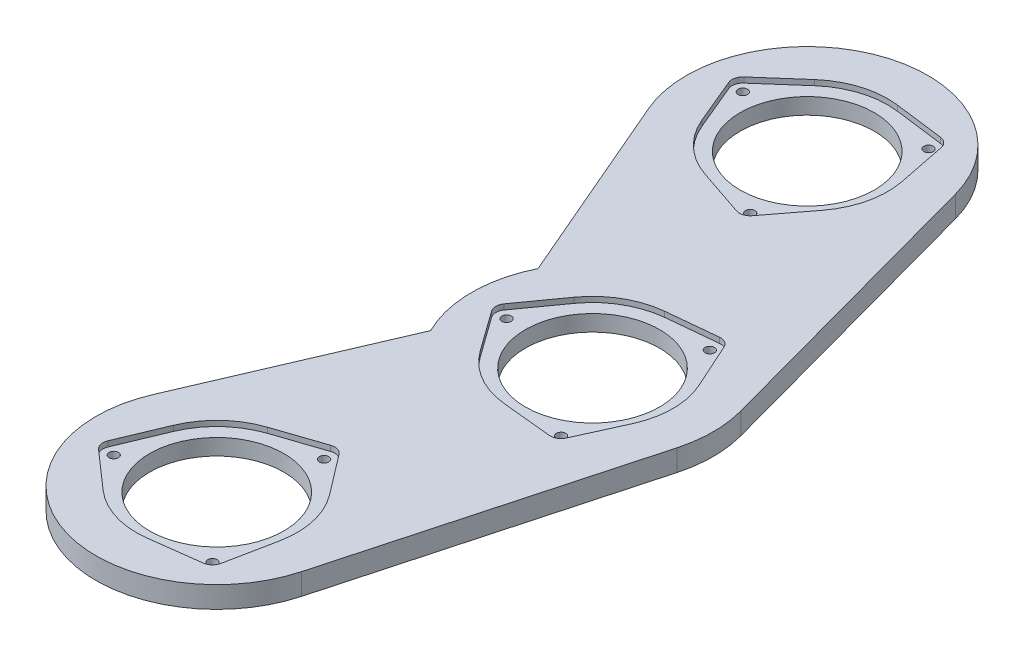
SolidWorks part; units mm, degrees
ref_plane "Alzado" through (0, 0, 0) normal (0, 0, 1) x (1, 0, 0)
ref_plane "Planta" through (0, 0, 0) normal (0, 1, 0) x (1, 0, 0)
ref_plane "Vista lateral" through (0, 0, 0) normal (1, 0, 0) x (0, 0, -1)
sketch "Croquis5" plane through (0, 0, 0) normal (0, 1, 0) x (1, 0, 0)
  line L0 (0, 176.3184) -> (0, -176.3184) construction
  line L1 (-217.2635, 0) -> (217.2635, 0) construction
  line L2 (13.4144, 121.8403) -> (43.4144, 11.8403)
  line L3 (43.4144, -11.8403) -> (13.4144, -121.8403)
  line L6 (-71.3458, 92.237) -> (-40.3113, 20)
  line L7 (-71.3458, -92.237) -> (-40.3113, -20)
  circle A0 centre (0, 0) radius 45
  circle A1 centre (-30, 110) radius 45
  circle A2 centre (-30, -110) radius 45
  point P6 (0, 0)
  point P9 (0, 0)
  point P21 (0, 0)
  point P22 (-34.641, 20)
  dimension "D1" = 90
  dimension "D2" = 220
  dimension "D3" = 30
  dimension "D4" = 20
sketch "Croquis1" plane through (0, 0, 0) normal (0, 1, 0) x (1, 0, 0)
  line L16 (-71.3458, 92.237) -> (-40.3113, 20) construction
  line L17 (-71.3458, -92.237) -> (-40.3113, -20) construction
  line L18 (43.4144, -11.8403) -> (13.4144, -121.8403) construction
  line L19 (13.4144, 121.8403) -> (43.4144, 11.8403) construction
  line L20 (-71.3458, 92.237) -> (-40.3113, 20)
  line L21 (-71.3458, -92.237) -> (-40.3113, -20)
  line L22 (43.4144, -11.8403) -> (13.4144, -121.8403)
  line L23 (13.4144, 121.8403) -> (43.4144, 11.8403)
  circle A10 centre (-30, -110) radius 45 construction
  circle A11 centre (0, 0) radius 45 construction
  circle A12 centre (-30, 110) radius 45 construction
  arc A13 (-71.3458, -92.237) -> (13.4144, -121.8403) centre (-30, -110) ccw
  arc A14 (-40.3113, 20) -> (-40.3113, -20) centre (0, 0) ccw
  arc A15 (13.4144, 121.8403) -> (-71.3458, 92.237) centre (-30, 110) ccw
  arc A16 (43.4144, -11.8403) -> (43.4144, 11.8403) centre (0, 0) ccw
extrude "Saliente-Extruir1" add sketch "Croquis1" along normal blind 8
sketch "Croquis6" plane through (0, 8, 0) normal (0, 1, 0) x (1, 0, 0)
  line L0 (-17.4639, -76.972) -> (-6.1488, -91.8033)
  line L1 (-39.5981, -81.5768) -> (-21.9239, -75.6085)
  line L2 (0, 0) -> (-32, 0) construction
  line L3 (-24.375, -17.4888) -> (-35.25, -2.3318)
  line L4 (-35.25, 2.3318) -> (-24.375, 17.4888)
  line L5 (-2.9583, 29.8538) -> (15.6056, 31.6933)
  line L6 (19.6444, 29.3615) -> (27.3333, 12.365)
  line L7 (27.3333, -12.365) -> (19.6444, -29.3615)
  line L8 (15.6056, -31.6933) -> (-2.9583, -29.8538)
  line L9 (-7.665, -137.3705) -> (-26.1668, -139.7541)
  line L10 (-49.8161, -132.5238) -> (-63.822, -120.2016)
  line L11 (-0.5858, -115.8994) -> (-4.2542, -134.1899)
  line L12 (-30, -110) -> (-61.1798, -117.1984) construction
  line L13 (-64.8711, -115.6574) -> (-57.6844, -98.4426)
  line L14 (-64.8711, 115.6574) -> (-57.6844, 98.4426)
  line L15 (-0.5858, 115.8994) -> (-4.2542, 134.1899)
  line L16 (-49.8161, 132.5238) -> (-63.822, 120.2016)
  line L17 (-7.665, 137.3705) -> (-26.1668, 139.7541)
  line L18 (-39.5981, 81.5768) -> (-21.9239, 75.6085)
  line L19 (-17.4639, 76.972) -> (-6.1488, 91.8033)
  arc A0 (-24.375, -17.4888) -> (-2.9583, -29.8538) centre (0, 0) ccw
  arc A3 (-35.25, 2.3318) -> (-35.25, -2.3318) centre (-32, 0) ccw
  arc A4 (19.6444, 29.3615) -> (15.6056, 31.6933) centre (16, 27.7128) ccw
  arc A5 (15.6056, -31.6933) -> (19.6444, -29.3615) centre (16, -27.7128) ccw
  arc A6 (-2.9583, 29.8538) -> (-24.375, 17.4888) centre (0, 0) ccw
  arc A8 (27.3333, -12.365) -> (27.3333, 12.365) centre (0, 0) ccw
  arc A9 (-39.5981, -81.5768) -> (-57.6844, -98.4426) centre (-30, -110) ccw
  arc A10 (-49.8161, -132.5238) -> (-26.1668, -139.7541) centre (-30, -110) ccw
  arc A11 (-17.4639, -76.972) -> (-21.9239, -75.6085) centre (-20.6441, -79.3982) ccw
  arc A12 (-0.5858, -115.8994) -> (-6.1488, -91.8033) centre (-30, -110) ccw
  arc A13 (-64.8711, -115.6574) -> (-63.822, -120.2016) centre (-61.1798, -117.1984) ccw
  arc A14 (-7.665, -137.3705) -> (-4.2542, -134.1899) centre (-8.1761, -133.4033) ccw
  arc A15 (-7.665, 137.3705) -> (-4.2542, 134.1899) centre (-8.1761, 133.4033) cw
  arc A16 (-64.8711, 115.6574) -> (-63.822, 120.2016) centre (-61.1798, 117.1984) cw
  arc A17 (-0.5858, 115.8994) -> (-6.1488, 91.8033) centre (-30, 110) cw
  arc A18 (-17.4639, 76.972) -> (-21.9239, 75.6085) centre (-20.6441, 79.3982) cw
  arc A19 (-49.8161, 132.5238) -> (-26.1668, 139.7541) centre (-30, 110) cw
  arc A20 (-39.5981, 81.5768) -> (-57.6844, 98.4426) centre (-30, 110) cw
  dimension "D1" = 60
  dimension "D2" = 8
  dimension "D3" = 32
  dimension "D5" = 60
  dimension "D6" = 8
  dimension "D7" = 32
  dimension "D4" = 3
extrude "Cortar-Extruir2" cut sketch "Croquis6" against normal blind 2
sketch "Croquis7" plane through (0, 6, 0) normal (0, 1, 0) x (1, 0, 0)
  line L0 (-217.2635, 0) -> (217.2635, 0) construction
  line L1 (-217.2635, 0) -> (217.2635, 0) construction
  circle A0 centre (-30, 110) radius 25
  circle A1 centre (-30, -110) radius 25
  circle A2 centre (0, 0) radius 25
  circle A5 centre (-61.1798, 117.1984) radius 1.75
  circle A6 centre (-8.1761, 133.4033) radius 1.75
  circle A7 centre (-20.6441, 79.3982) radius 1.75
  circle A8 centre (16, 27.7128) radius 1.75
  circle A9 centre (-32, 0) radius 1.75
  circle A10 centre (16, -27.7128) radius 1.75
  circle A11 centre (-8.1761, -133.4033) radius 1.75
  circle A12 centre (-61.1798, -117.1984) radius 1.75
  circle A13 centre (-20.6441, -79.3982) radius 1.75
  point P15 (-8.1761, 133.4033)
  point P21 (-20.6441, 79.3982)
  point P25 (16, 27.7128)
  point P29 (-32, 0)
  point P33 (16, -27.7128)
  point P37 (-8.1761, -133.4033)
  point P41 (-61.1798, -117.1984)
  point P45 (-20.6441, -79.3982)
  dimension "D1" = 50
  dimension "D2" = 3.5
extrude "Cortar-Extruir3" cut sketch "Croquis7" against normal through all both and the other way through all
sketch "Croquis3" plane through (0, 0, 0) normal (0, 1, 0) x (1, 0, 0)
  line L0 (-88.2271, 0) -> (88.2271, 0) construction
  line L2 (4.0415, -7) -> (8.0829, 0)
  line L3 (8.0829, 0) -> (4.0415, 7)
  line L4 (4.0415, 7) -> (-4.0415, 7)
  line L5 (-4.0415, 7) -> (-8.0829, 0)
  line L6 (-8.0829, 0) -> (-4.0415, -7)
  line L7 (-4.0415, -7) -> (4.0415, -7)
  line L8 (-15.9585, 103) -> (-11.9171, 110)
  line L9 (-11.9171, 110) -> (-15.9585, 117)
  line L10 (-15.9585, 117) -> (-24.0415, 117)
  line L11 (-24.0415, 117) -> (-28.0829, 110)
  line L12 (-28.0829, 110) -> (-24.0415, 103)
  line L13 (-24.0415, 103) -> (-15.9585, 103)
  line L14 (-15.9585, -117) -> (-11.9171, -110)
  line L15 (-11.9171, -110) -> (-15.9585, -103)
  line L16 (-15.9585, -103) -> (-24.0415, -103)
  line L17 (-24.0415, -103) -> (-28.0829, -110)
  line L18 (-28.0829, -110) -> (-24.0415, -117)
  line L19 (-24.0415, -117) -> (-15.9585, -117)
  circle A0 centre (0, 0) radius 5 construction
  circle A2 centre (-20, 110) radius 5 construction
  circle A3 centre (-20, -110) radius 5 construction
  arc A4 (4.5967, 114.4721) -> (-44.5967, 105.5279) centre (-20, 110) ccw construction
  circle A5 centre (0, 0) radius 7 construction
  circle A6 centre (-20, 110) radius 7 construction
  circle A7 centre (-20, -110) radius 7 construction
  point P9 (0, 0)
  dimension "D1" = 14
extrude "Cortar-Extruir1" [suppressed] cut sketch "Croquis3" along normal through all both and the other way through all
sketch "Croquis4" [suppressed] plane through (0, 8, 0) normal (0, -1, 0) x (1, 0, 0)
  line L0 (-88.2271, 0) -> (88.2271, 0) construction
  line L7 (-11.9171, 110) -> (-15.9585, 103) construction
  line L8 (-15.9585, 117) -> (-11.9171, 110) construction
  line L9 (-15.9585, 103) -> (-24.0415, 103) construction
  line L10 (-24.0415, 103) -> (-28.0829, 110) construction
  line L11 (-28.0829, 110) -> (-24.0415, 117) construction
  line L12 (-24.0415, 117) -> (-15.9585, 117) construction
  line L13 (-11.9171, 110) -> (-15.9585, 103)
  line L14 (-15.9585, 117) -> (-11.9171, 110)
  line L15 (-15.9585, 103) -> (-24.0415, 103)
  line L16 (-24.0415, 103) -> (-28.0829, 110)
  line L17 (-28.0829, 110) -> (-24.0415, 117)
  line L18 (-24.0415, 117) -> (-21, 117)
  line L32 (4.0415, 7) -> (8.0829, 0) construction
  line L39 (8.0829, 0) -> (4.0415, -7) construction
  line L40 (4.0415, -7) -> (-4.0415, -7) construction
  line L41 (-4.0415, -7) -> (-8.0829, 0) construction
  line L42 (-8.0829, 0) -> (-4.0415, 7) construction
  line L43 (-4.0415, 7) -> (4.0415, 7) construction
  line L44 (4.0415, 7) -> (8.0829, 0)
  line L45 (8.0829, 0) -> (4.0415, -7)
  line L46 (4.0415, -7) -> (-4.0415, -7)
  line L47 (-4.0415, -7) -> (-8.0829, 0)
  line L48 (-8.0829, 0) -> (-4.0415, 7)
  line L49 (-4.0415, 7) -> (-1, 7)
  line L50 (-20, 117) -> (-20, 123) construction
  line L51 (-21, 117) -> (-21, 122.9615)
  line L52 (-19, 117) -> (-19, 122.9615)
  line L53 (-19, 117) -> (-15.9585, 117)
  line L54 (4.4, 0) -> (-4.4, 0) construction
  line L55 (-21, -117) -> (-21, -122.9615)
  line L56 (-19, -117) -> (-19, -122.9615)
  line L57 (-19, -117) -> (-15.9585, -117)
  line L58 (-24.0415, -117) -> (-21, -117)
  line L59 (-28.0829, -110) -> (-24.0415, -117)
  line L60 (-24.0415, -103) -> (-28.0829, -110)
  line L61 (-15.9585, -103) -> (-24.0415, -103)
  line L62 (-11.9171, -110) -> (-15.9585, -103)
  line L63 (-15.9585, -117) -> (-11.9171, -110)
  line L64 (0, 7) -> (0, 13) construction
  line L65 (-1, 7) -> (-1, 12.9615)
  line L66 (1, 7) -> (1, 12.9615)
  line L67 (1, 7) -> (4.0415, 7)
  arc A0 (-21, 122.9615) -> (-19, 122.9615) centre (-20, 110) ccw
  arc A2 (-1, 12.9615) -> (1, 12.9615) centre (0, 0) ccw
  arc A3 (-21, -122.9615) -> (-19, -122.9615) centre (-20, -110) cw
  dimension "D1" = 26
  dimension "D2" = 2
  dimension "D3" = 2
extrude "Saliente-Extruir2" [suppressed] add sketch "Croquis4" against normal blind 10
